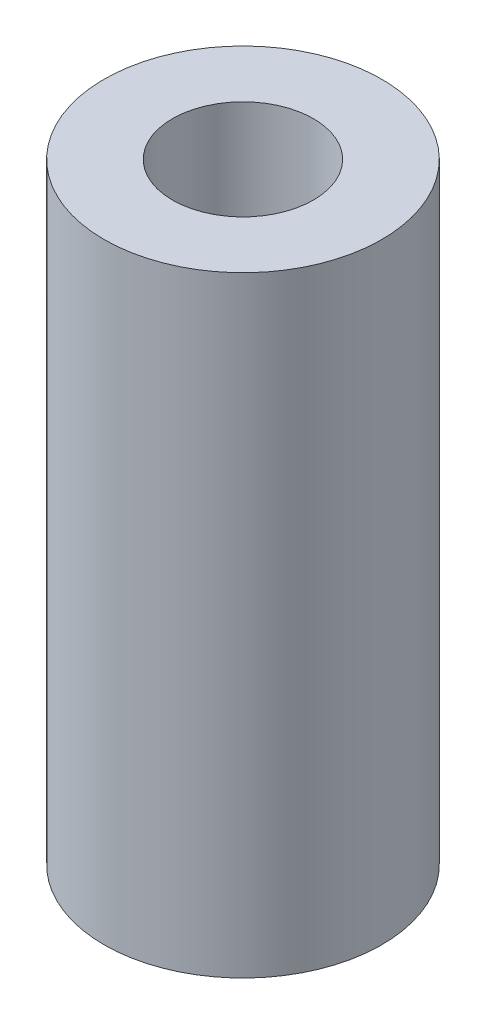
SolidWorks part; units mm, degrees
ref_plane "Front Plane" through (0, 0, 0) normal (0, 0, 1) x (1, 0, 0)
ref_plane "Top Plane" through (0, 0, 0) normal (0, 1, 0) x (1, 0, 0)
ref_plane "Right Plane" through (0, 0, 0) normal (1, 0, 0) x (0, 0, -1)
sketch "Sketch1" plane through (0, 0, 0) normal (0, 1, 0) x (1, 0, 0)
  circle A0 centre (0, 0) radius 6.35
  arc A4 (5.6286, -2.9396) -> (-4.0286, 4.9085) centre (0, 0) ccw construction
  circle A5 centre (0, 0) radius 3.2258
  circle A6 centre (0, 0) radius 3.2258
  dimension "D1" = 0.0508
extrude "Boss-Extrude1" add sketch "Sketch1" along normal up to surface (27.9373 mm away)
